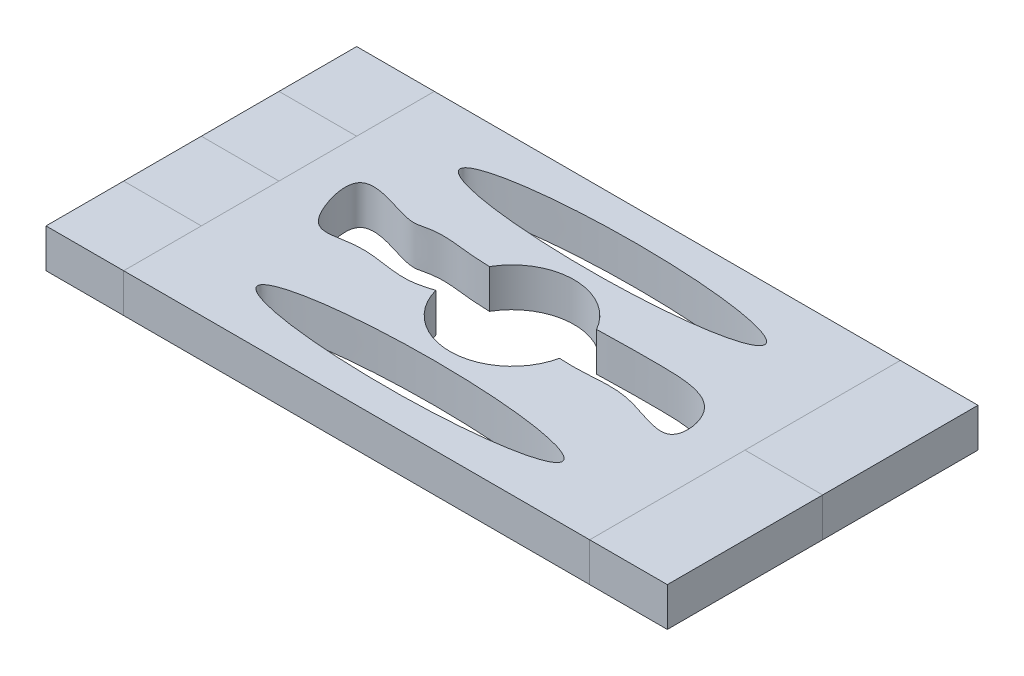
SolidWorks part; units mm, degrees
other "Markup1"
sketch "Sketch6" plane through (-31.75, 3.175, -12.7) normal (0, 1, 0) x (1, 0, 0)
material "6061 Alloy"
ref_plane "Front Plane" through (0, 0, 0) normal (0, 0, 1) x (1, 0, 0)
ref_plane "Top Plane" through (0, 0, 0) normal (0, 1, 0) x (1, 0, 0)
ref_plane "Right Plane" through (0, 0, 0) normal (1, 0, 0) x (0, 0, -1)
sketch "Sketch1" plane through (0, 0, 0) normal (0, 1, 0) x (1, 0, 0)
  line L1 (-19.05, -12.7) -> (19.05, -12.7)
  line L2 (-19.05, -12.7) -> (-19.05, 12.7)
  line L3 (-19.05, 12.7) -> (19.05, 12.7)
  line L4 (19.05, -12.7) -> (19.05, 12.7)
  line L5 (-19.05, -12.7) -> (19.05, 12.7) construction
  line L6 (-19.05, 12.7) -> (19.05, -12.7) construction
  circle A0 centre (0, 0) radius 5.08
  point P0 (0, 0)
  dimension "D3" = 10.16
  dimension "D1" = 38.1
  dimension "D2" = 25.4
extrude "Boss-Extrude1" add sketch "Sketch1" along normal blind 3.175
sketch "Sketch2" plane through (-19.05, 0, 0) normal (-1, 0, 0) x (0, 0, 1)
  line L0 (-12.7, 0) -> (12.7, 0) construction
  line L3 (-12.7, 3.175) -> (-6.35, 3.175)
  line L4 (-12.7, 3.175) -> (-12.7, 0)
  line L5 (-12.7, 0) -> (-6.35, 0)
  line L6 (-6.35, 3.175) -> (-6.35, 0)
  line L7 (-12.7, 3.175) -> (12.7, 3.175) construction
  line L8 (-6.35, 0) -> (0, 0)
  line L9 (-6.35, 0) -> (-6.35, 3.175)
  line L10 (-6.35, 3.175) -> (0, 3.175)
  line L11 (0, 0) -> (0, 3.175)
  line L13 (0, 3.175) -> (6.35, 3.175)
  line L14 (0, 3.175) -> (0, 0)
  line L15 (0, 0) -> (6.35, 0)
  line L16 (6.35, 3.175) -> (6.35, 0)
  line L17 (6.35, 3.175) -> (12.7, 3.175)
  line L18 (6.35, 3.175) -> (6.35, 0)
  line L19 (6.35, 0) -> (12.7, 0)
  line L20 (12.7, 3.175) -> (12.7, 0)
  line M11 (-12.7, 0) -> (12.7, 0)
  line M12 (12.7, 0) -> (12.7, 3.175)
  line M13 (12.7, 3.175) -> (-12.7, 3.175)
  line M14 (-12.7, 3.175) -> (-12.7, 0)
  dimension "D1" = 6.35
  dimension "D2" = 6.35
extrude "Boss-Extrude3" add sketch "Sketch2" along normal blind 6.35 separate body contours L6 M13 M14 M11 region at (-19.05, 1.5875, -9.525)
extrude "Boss-Extrude4" add sketch "Sketch2<4>" along normal blind 6.35 separate body contours L11 L6 M11 M13 region at (-19.05, 1.5875, -3.175)
sketch "Sketch2<4>" plane through (-19.05, 0, 0) normal (-1, 0, 0) x (0, 0, 1) same geometry as "Sketch2"
extrude "Boss-Extrude6" add sketch "Sketch2<6>" along normal blind 6.35 separate body contours L16 L11 M13 M11 region at (-19.05, 1.5875, 3.175)
sketch "Sketch2<6>" plane through (-19.05, 0, 0) normal (-1, 0, 0) x (0, 0, 1) same geometry as "Sketch2"
extrude "Boss-Extrude7" add sketch "Sketch2<7>" along normal blind 6.35 separate body contours L16 M13 M11 M12 region at (-19.05, 1.5875, 9.525)
sketch "Sketch2<7>" plane through (-19.05, 0, 0) normal (-1, 0, 0) x (0, 0, 1) same geometry as "Sketch2"
sketch "Sketch4" plane through (19.05, 0, 0) normal (1, 0, 0) x (0, 0, -1)
  line L0 (-12.7, 0) -> (12.7, 0) construction
  line L1 (-12.7, 0) -> (0, 0)
  line L2 (-12.7, 0) -> (-12.7, 3.175)
  line L3 (-12.7, 3.175) -> (0, 3.175)
  line L4 (0, 0) -> (0, 3.175)
  line L5 (-12.7, 3.175) -> (-12.7, 0) construction
  line L6 (-12.7, 3.175) -> (12.7, 3.175) construction
  line L8 (0, 3.175) -> (12.7, 3.175)
  line L9 (0, 3.175) -> (0, 0)
  line L10 (0, 0) -> (12.7, 0)
  line L11 (12.7, 3.175) -> (12.7, 0)
  line M1 (-12.7, 0) -> (12.7, 0)
  line M2 (12.7, 0) -> (12.7, 3.175)
  line M3 (12.7, 3.175) -> (-12.7, 3.175)
  line M4 (-12.7, 3.175) -> (-12.7, 0)
extrude "Boss-Extrude8" add sketch "Sketch4" along normal blind 6.35 separate body contours L4 M1 M3 M4 region at (19.05, 1.5875, 6.35)
extrude "Boss-Extrude9" add sketch "Sketch4<3>" along normal blind 6.35 separate body contours L4 M1 M2 M3 region at (19.05, 1.5875, -6.35)
sketch "Sketch4<3>" plane through (19.05, 0, 0) normal (1, 0, 0) x (0, 0, -1) same geometry as "Sketch4"
sketch "Sketch9" plane through (0, 3.175, 0) normal (0, 1, 0) x (1, 0, 0)
  line L0 (-1.7463, 0) -> (1.7463, 0) construction
  ellipse E0 centre (-0.0639, 8.2771) end of major axis (12.388, 8.2771) minor radius 1.9175
  ellipse E1 centre (-0.0639, -8.2771) end of major axis (12.388, -8.2771) minor radius 1.9175
  point P14 (12.388, 8.2771)
extrude "Cut-Extrude5" cut sketch "Sketch9" against normal through all
sketch "Sketch10" plane through (0, 3.175, 0) normal (0, 1, 0) x (1, 0, 0)
  spline S0 degree 3 poles (-5.7229, 2.5814) (-10.3073, 3.1667) (-9.3236, 1.6388) (-16.5675, 4.5894) (-15.6696, 0.2542) (-14.16, -2.1222) (-10.5892, -0.9114) (-7.0567, -2.3118) (-1.4928, 0.2054) (5.1981, -1.6692) (10.4339, -0.4722) (15.8354, -3.4502) (14.9813, 2.4474) (8.6203, 2.5636) (7.2971, 2.5386) (1.1319, 2.3834) (-5.7229, 2.5814) (-10.3073, 3.1667) (-9.3236, 1.6388) knots -0.165547 -0.028084 -0.002808 0 0.085842 0.139398 0.182102 0.208315 0.24297 0.308418 0.352477 0.474806 0.546687 0.622661 0.680218 0.746905 0.834453 0.971916 0.997192 1 1.085842 1.139398 1.182102 only from (-6.9618, 2.7387) to (-6.9618, 2.7387)
  point P2 (-15.357, 0)
  point P4 (-14.1284, -1.5613)
  point P6 (-6.5523, -1.7149)
  point P8 (-6.9618, 2.7387)
  point P10 (13.0534, 2.5851)
  point P12 (14.9986, -1.8172)
  point P14 (10.5963, -1.1518)
  point P16 (14.3332, 1.4077)
  point P18 (9.982, 2.5339)
extrude "Cut-Extrude7" cut sketch "Sketch10" against normal through all contours S0
